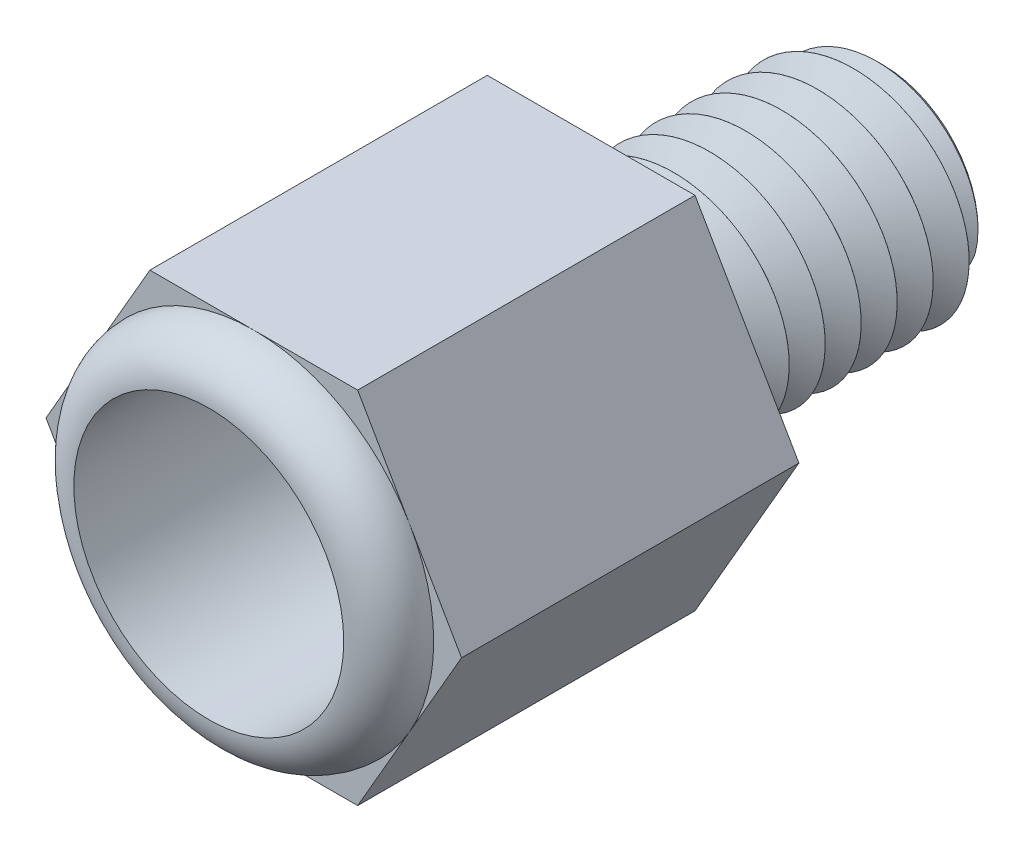
SolidWorks part; units mm, degrees
material "Bronze commercial, UNS C22000 (90-10 Bronze)"
ref_plane "Plan de face" through (0, 0, 0) normal (0, 0, 1) x (1, 0, 0)
ref_plane "Plan de dessus" through (0, 0, 0) normal (0, 1, 0) x (1, 0, 0)
ref_plane "Plan de droite" through (0, 0, 0) normal (1, 0, 0) x (0, 0, -1)
ref_plane "Plan1" through (0, 0, -0.8) normal (0, 0, 1) x (1, 0, 0)
sketch "Esquisse1" plane through (0, 0, 0) normal (0, 0, 1) x (1, 0, 0)
  line L1 (1.7321, 0) -> (0.866, 1.5)
  line L2 (0.866, 1.5) -> (-0.866, 1.5)
  line L3 (-0.866, 1.5) -> (-1.7321, 0)
  line L4 (-1.7321, 0) -> (-0.866, -1.5)
  line L5 (-0.866, -1.5) -> (0.866, -1.5)
  line L6 (0.866, -1.5) -> (1.7321, 0)
  circle A0 centre (0, 0) radius 2.5
  circle A1 centre (0, 0) radius 1.5 construction
  dimension "D1" = 5
  dimension "D2" = 3
extrude "Boss.-Extru.1" add sketch "Esquisse1" along normal blind 6.5
sketch "Forme" plane through (0, 0, 0) normal (1, 0, 0) x (0, 0, -1)
  line L0 (0, -1.808) -> (-0.3995, -2.5)
  line L1 (0, -2.5) -> (0, 2.5) construction
  line L2 (-0.3995, -2.5) -> (0.3995, -2.5)
  line L3 (0.3995, -2.5) -> (0, -1.808)
  line L4 (-6.5, -2.5) -> (0, -2.5) construction
  dimension "D1" = 60
  dimension "D2" = 0.799
sketch "Esquisse3" plane through (0, 0, -0.8) normal (0, 0, -1) x (-1, 0, 0)
  circle A0 centre (0, 0) radius 2.5
  dimension "D1" = 5
curve "Hélice/Spirale1" pitch 0.8 height 7 radius 2.5 centre (0, 0, -0.8) axis (0, 0, 1) start towards (-1, 0, 0)
chamfer "Chanfrein1" distance 0.4 angle 45 1 edges at (2.5, 0, 0)
sweep "Filetage M5" cut profiles "Forme" path "Hélice/Spirale1"
sketch "Esquisse4" plane through (0, 0, 0) normal (0, 0, -1) x (-1, 0, 0)
  circle A0 centre (0, 0) radius 1.8
  dimension "D1" = 3.6
extrude "Enlèv. mat.-Extru.1" cut sketch "Esquisse4" against normal blind 2.3
sketch "Esquisse5" plane through (0, 0, 6.5) normal (0, 0, 1) x (1, 0, 0)
  line L1 (4.6188, 0) -> (2.3094, 4)
  line L2 (2.3094, 4) -> (-2.3094, 4)
  line L3 (-2.3094, 4) -> (-4.6188, 0)
  line L4 (-4.6188, 0) -> (-2.3094, -4)
  line L5 (-2.3094, -4) -> (2.3094, -4)
  line L6 (2.3094, -4) -> (4.6188, 0)
  circle A0 centre (0, 0) radius 4 construction
  circle A1 centre (0, 0) radius 1.7821
  dimension "D1" = 8
  dimension "D2" = 3.5641
extrude "Boss.-Extru.2" add sketch "Esquisse5" along normal blind 7.5
sketch "Esquisse6" plane through (0, 0, 14) normal (0, 0, 1) x (1, 0, 0)
  circle A0 centre (0, 0) radius 1.7821
  circle A1 centre (0, 0) radius 4
  dimension "D1" = 3.5641
  dimension "D2" = 8
extrude "Boss.-Extru.3" add sketch "Esquisse6" along normal blind 1
fillet "Congé1" radius 1 1 edges at (4, 0, 15)
sketch "Esquisse7" plane through (0, 0, 15) normal (0, 0, 1) x (1, 0, 0)
  circle A0 centre (0, 0) radius 3
  dimension "D1" = 6
extrude "Enlèv. mat.-Extru.2" cut sketch "Esquisse7" against normal blind 5
